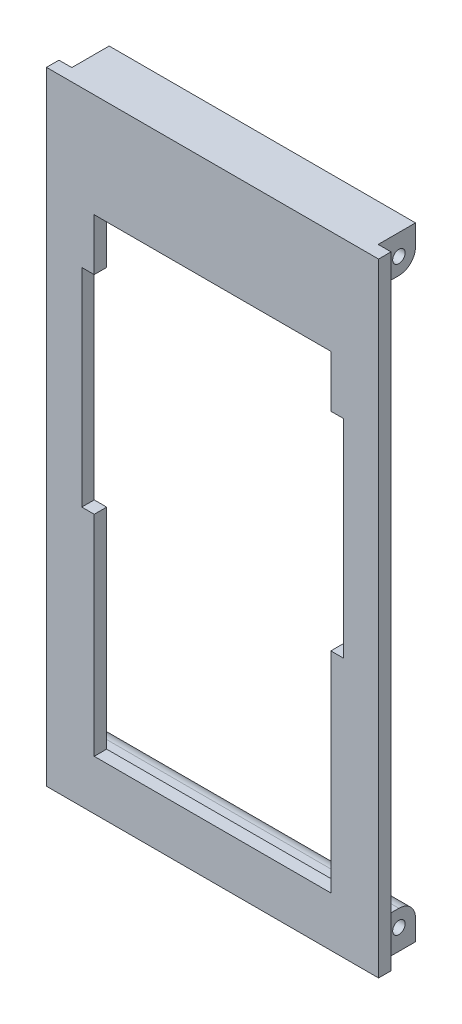
SolidWorks part; units mm, degrees
ref_plane "Front Plane" through (0, 0, 0) normal (0, 0, 1) x (1, 0, 0)
ref_plane "Top Plane" through (0, 0, 0) normal (0, 1, 0) x (1, 0, 0)
ref_plane "Right Plane" through (0, 0, 0) normal (1, 0, 0) x (0, 0, -1)
sketch "Sketch3" plane through (0, 0, 0) normal (1, 0, 0) x (0, 0, -1)
  line L0 (0, 150) -> (12, 150)
  line L2 (0, 0) -> (0, 150)
  line L4 (3, 9) -> (3, 141)
  line L7 (3, 141) -> (12, 141)
  line L8 (12, 150) -> (12, 141)
  line L11 (3, 9) -> (12, 9)
  line L12 (12, 0) -> (12, 9)
  line L13 (0, 0) -> (12, 0)
  circle A0 centre (8, 145) radius 1.5
  circle A1 centre (8, 5) radius 1.5
  dimension "D2" = 3
  dimension "D3" = 3
  dimension "D1" = 3
  dimension "D4" = 150
  dimension "D5" = 5
  dimension "D6" = 8
  dimension "D7" = 4
  dimension "D8" = 4
  dimension "D9" = 4
  dimension "D10" = 8
  dimension "D11" = 4
  dimension "D12" = 5
extrude "Boss-Extrude3" add sketch "Sketch3" along normal blind 80 separate body
sketch "Sketch4" plane through (0, 0, 0) normal (0, 0, 1) x (1, 0, 0)
  line L0 (0, 0) -> (80, 0) construction
  line L1 (40, 0) -> (40, 175) construction
  line L2 (11.5, 112.5) -> (11.5, 125)
  line L3 (11.5, 12) -> (68.5, 12)
  line L4 (11.5, 12) -> (11.5, 62.5)
  line L5 (11.5, 125) -> (68.5, 125)
  line L6 (68.5, 12) -> (68.5, 62.5)
  line L7 (11.5, 12) -> (68.5, 125) construction
  line L8 (11.5, 125) -> (68.5, 12) construction
  line L9 (8.5, 62.5) -> (11.5, 62.5)
  line L10 (8.5, 62.5) -> (8.5, 112.5)
  line L11 (8.5, 112.5) -> (11.5, 112.5)
  line L12 (71.5, 62.5) -> (71.5, 112.5)
  line L13 (8.5, 62.5) -> (71.5, 112.5) construction
  line L14 (8.5, 112.5) -> (71.5, 62.5) construction
  line L15 (68.5, 112.5) -> (71.5, 112.5)
  line L16 (68.5, 112.5) -> (68.5, 125)
  line L17 (68.5, 62.5) -> (71.5, 62.5)
  line L18 (80, 150) -> (0, 150) construction
  point P6 (40, 68.5)
  point P11 (40, 87.5)
  dimension "D1" = 25
  dimension "D2" = 12
  dimension "D3" = 3
  dimension "D4" = 12.5
  dimension "D5" = 50
  dimension "D6" = 57
extrude "Cut-Extrude1" cut sketch "Sketch4" against normal through all
sketch "Sketch5" plane through (0, 0, 0) normal (0, 1, 0) x (1, 0, 0)
  line L0 (0, 0) -> (80, 0) construction
  line L1 (80, 3) -> (76.9, 3)
  line L2 (40, 0) -> (40, 22.0256) construction
  line L3 (0, 12) -> (3.1, 12)
  line L4 (0, 12) -> (0, 3)
  line L5 (0, 3) -> (3.1, 3)
  line L6 (3.1, 12) -> (3.1, 3)
  line L7 (76.9, 12) -> (76.9, 3)
  line L8 (80, 12) -> (76.9, 12)
  line L9 (80, 12) -> (80, 3)
  dimension "D1" = 3
  dimension "D2" = 3.1
extrude "Cut-Extrude2" cut sketch "Sketch5" along normal through all contours L4 L5 L6 L3 | L1 L7 L8 L9
fillet "Fillet1" radius 4 2 edges at (40, 141, -12) (40, 9, -12)
